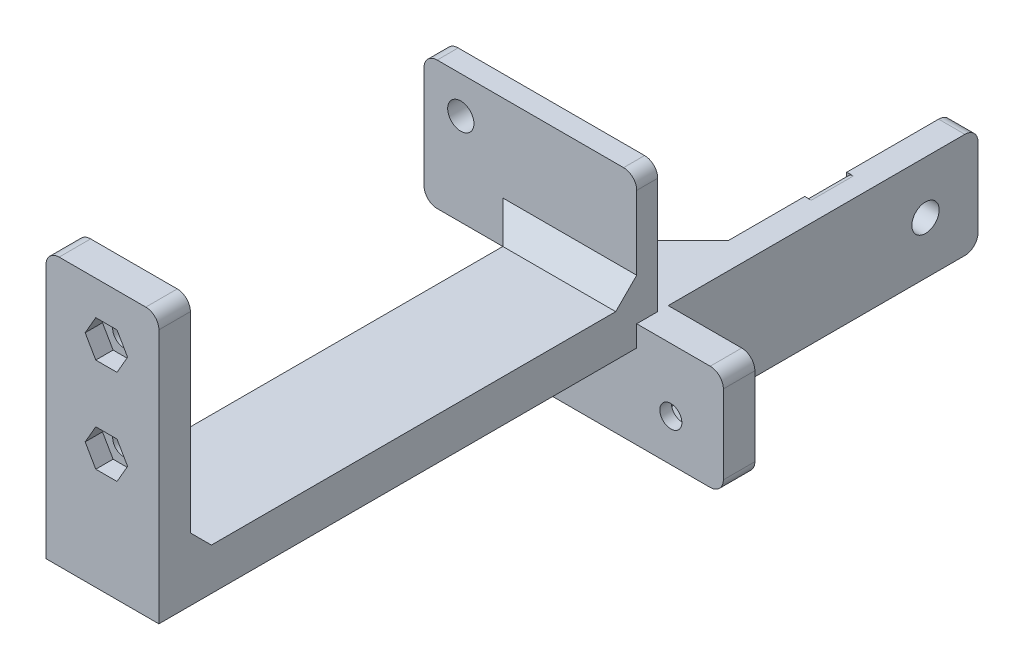
SolidWorks part; units mm, degrees
ref_plane "Спереди" through (0, 0, 0) normal (0, 0, 1) x (1, 0, 0)
ref_plane "Сверху" through (0, 0, 0) normal (0, 1, 0) x (1, 0, 0)
ref_plane "Справа" through (0, 0, 0) normal (1, 0, 0) x (0, 0, -1)
sketch "Эскиз3" plane through (0, 0, 0) normal (0, 0, 1) x (1, 0, 0)
  line L0 (-19, -10) -> (19, 10) construction
  line L1 (-19, 10) -> (19, 10)
  line L2 (-19, 10) -> (-19, -10)
  line L3 (-19, -10) -> (19, -10)
  line L4 (19, 10) -> (19, -10)
  point P4 (0, 0)
  dimension "D1" = 38
  dimension "D2" = 20
extrude "Бобышка-Вытянуть1" add sketch "Эскиз3" along normal blind 6
sketch "Эскиз4" plane through (-10.8, 0, 0) normal (0, 0, 1) x (1, 0, 0)
  line L11 (-8.2, -10) -> (29.8, -10) construction
  line L12 (8.3, -10) -> (13.3, -10)
  line L14 (8.3, -10) -> (8.3, 10)
  line L15 (8.3, 10) -> (13.3, 10)
  line L16 (13.3, -10) -> (13.3, 10)
  line L17 (29.8, 10) -> (-8.2, 10) construction
  line L18 (-8.2, 10) -> (-8.2, -10) construction
  point P12 (10.8, 10)
  point P13 (10.8, 10)
  dimension "D1" = 16.5
  dimension "D2" = 5
extrude "Бобышка-Вытянуть2" add sketch "Эскиз4" against normal blind 59
sketch "Эскиз9" plane through (0, 0, 6) normal (0, 0, 1) x (1, 0, 0)
  line L1 (2.5, 10) -> (-38, 10)
  line L2 (2.5, 10) -> (2.5, 34.5)
  line L3 (2.5, 34.5) -> (-38, 34.5)
  line L4 (-38, 10) -> (-38, 34.5)
  line L7 (19, 10) -> (-19, 10) construction
  dimension "D1" = 40.5
  dimension "D2" = 5
  dimension "D3" = 24.5
extrude "Бобышка-Вытянуть4" add sketch "Эскиз9" against normal blind 4
sketch "Эскиз12" plane through (0, 10, 0) normal (0, 1, 0) x (-1, 0, 0)
  line L0 (-2.5, 2) -> (-2.5, 6) construction
  line L1 (19, 6) -> (-2.5, 6)
  line L2 (19, 6) -> (19, 91)
  line L3 (19, 91) -> (-2.5, 91)
  line L4 (-2.5, 6) -> (-2.5, 91)
  line L5 (-19, 6) -> (-2.5, 6) construction
  dimension "D1" = 85
extrude "Бобышка-Вытянуть5" add sketch "Эскиз12" along normal mid plane 8
sketch "Эскиз13" plane through (0, 0, 91) normal (0, 0, 1) x (1, 0, 0)
  line L0 (2.5, 14) -> (-19, 14) construction
  line L1 (2.5, 6) -> (-19, 6)
  line L2 (2.5, 6) -> (2.5, 57)
  line L3 (2.5, 57) -> (-19, 57)
  line L4 (-19, 6) -> (-19, 57)
  dimension "D1" = 43
extrude "Бобышка-Вытянуть6" add sketch "Эскиз13" along normal blind 6
sketch "Эскиз23" plane through (0, 10, 0) normal (0, 1, 0) x (1, 0, 0)
  line L0 (-2.5, 16.5) -> (-19, 0)
  line L1 (-2.5, 59) -> (-2.5, 0) construction
  line L2 (-2.5, 0) -> (-19, 0) construction
  line L3 (-2.5, 16.5) -> (-2.5, 0)
  line L4 (-2.5, 0) -> (-19, 0)
  dimension "D1" = 45
extrude "Бобышка-Вытянуть8" add sketch "Эскиз23" against normal blind 4
sketch "Эскиз21" plane through (0, 0, -59) normal (0, 0, -1) x (-1, 0, 0)
  line L0 (2.5, 10) -> (2.5, -10) construction
  line L2 (1.25, 10) -> (2.5, 10)
  line L3 (2.5, 10) -> (2.5, 8.75)
  arc A0 (2.5, 8.75) -> (1.25, 10) centre (1.25, 8.75) ccw
  dimension "D1" = 2.5
extrude "Вырез-Вытянуть7" cut sketch "Эскиз21" against normal blind 8 from offset 20 offset against normal yes
sketch "Эскиз5" plane through (0, 0, 6) normal (0, 0, 1) x (1, 0, 0)
  line L0 (-9, -2) -> (9, -2) construction
  line L2 (19, 10) -> (2.5, 10) construction
  line L3 (2.5, 6) -> (-19, 6) construction
  circle A0 centre (-9, -2) radius 2.1
  circle A1 centre (9, -2) radius 2.1
  point P9 (0, -2)
  dimension "D1" = 4.2
  dimension "D2" = 4.2
  dimension "D3" = 18
  dimension "D4" = 12
  dimension "D5" = 8
extrude "Вырез-Вытянуть1" cut sketch "Эскиз5" against normal through all
sketch "Эскиз6" plane through (0, 0, 0) normal (0, 0, -1) x (-1, 0, 0)
  line L1 (-9, 2.1569) -> (-12.6, 0.0785)
  line L2 (-12.6, 0.0785) -> (-12.6, -4.0785)
  line L3 (-12.6, -4.0785) -> (-9, -6.1569)
  line L4 (-9, -6.1569) -> (-5.4, -4.0785)
  line L5 (-5.4, -4.0785) -> (-5.4, 0.0785)
  line L6 (-5.4, 0.0785) -> (-9, 2.1569)
  line L7 (9, 2.1569) -> (5.4, 0.0785)
  line L8 (5.4, 0.0785) -> (5.4, -4.0785)
  line L9 (5.4, -4.0785) -> (9, -6.1569)
  line L10 (9, -6.1569) -> (12.6, -4.0785)
  line L11 (12.6, -4.0785) -> (12.6, 0.0785)
  line L12 (12.6, 0.0785) -> (9, 2.1569)
  circle A0 centre (-9, -2) radius 3.6 construction
  circle A1 centre (9, -2) radius 3.6 construction
  dimension "D1" = 7.2
extrude "Вырез-Вытянуть2" cut sketch "Эскиз6" against normal blind 3.8
sketch "Эскиз7" plane through (2.5, 0, 0) normal (1, 0, 0) x (0, 0, -1)
  line L2 (59, 10) -> (59, -10) construction
  line L3 (59, -10) -> (0, -10) construction
  circle A0 centre (49, 0) radius 2.6
  dimension "D1" = 5.2
  dimension "D2" = 10
  dimension "D3" = 10
extrude "Вырез-Вытянуть3" cut sketch "Эскиз7" against normal through all
sketch "Эскиз17" plane through (0, 0, 91) normal (0, 0, -1) x (-1, 0, 0)
  line L0 (7.5, 29) -> (7.5, 47) construction
  line L1 (-2.5, 57) -> (19, 57) construction
  line L2 (-2.5, 14) -> (19, 14) construction
  line L3 (-2.5, 14) -> (-2.5, 57) construction
  circle A0 centre (7.5, 29) radius 2.1
  circle A1 centre (7.5, 47) radius 2.1
  dimension "D1" = 18
  dimension "D2" = 4.2
  dimension "D4" = 15
  dimension "D5" = 10
  dimension "D3" = 10
extrude "Вырез-Вытянуть4" cut sketch "Эскиз17" against normal through all
sketch "Эскиз18" plane through (0, 0, 97) normal (0, 0, 1) x (1, 0, 0)
  line L1 (-3.4585, 29) -> (-5.4793, 32.5)
  line L2 (-5.4793, 32.5) -> (-9.5207, 32.5)
  line L3 (-9.5207, 32.5) -> (-11.5415, 29)
  line L4 (-11.5415, 29) -> (-9.5207, 25.5)
  line L5 (-9.5207, 25.5) -> (-5.4793, 25.5)
  line L6 (-5.4793, 25.5) -> (-3.4585, 29)
  line L7 (-3.4585, 47) -> (-5.4793, 50.5)
  line L8 (-5.4793, 50.5) -> (-9.5207, 50.5)
  line L9 (-9.5207, 50.5) -> (-11.5415, 47)
  line L10 (-11.5415, 47) -> (-9.5207, 43.5)
  line L11 (-9.5207, 43.5) -> (-5.4793, 43.5)
  line L12 (-5.4793, 43.5) -> (-3.4585, 47)
  circle A0 centre (-7.5, 29) radius 3.5 construction
  circle A1 centre (-7.5, 47) radius 3.5 construction
  dimension "D1" = 7
extrude "Вырез-Вытянуть5" cut sketch "Эскиз18" against normal blind 3.3
sketch "Эскиз19" plane through (0, 0, 2) normal (0, 0, -1) x (-1, 0, 0)
  line L2 (38, 34.5) -> (38, 10) construction
  line L3 (-2.5, 34.5) -> (38, 34.5) construction
  circle A2 centre (31, 27.5) radius 2.5
  dimension "D4" = 7
  dimension "D5" = 7
extrude "Вырез-Вытянуть6" cut sketch "Эскиз19" against normal through all
fillet "Скругление2" radius 2.5 10 edges at (-19, 57, 94) (2.5, 57, 94) (19, 10, 3) (19, -10, 3) (-19, -10, 3) (-38, 34.5, 4) (-38, 10, 4) (2.5, 34.5, 4) (0, -10, -59) (0, 10, -59)
chamfer "Фаска2" distance 4 angle 45 3 edges at (-8.25, 14, 91) (-19, 12, 6) (-8.25, 14, 6)
